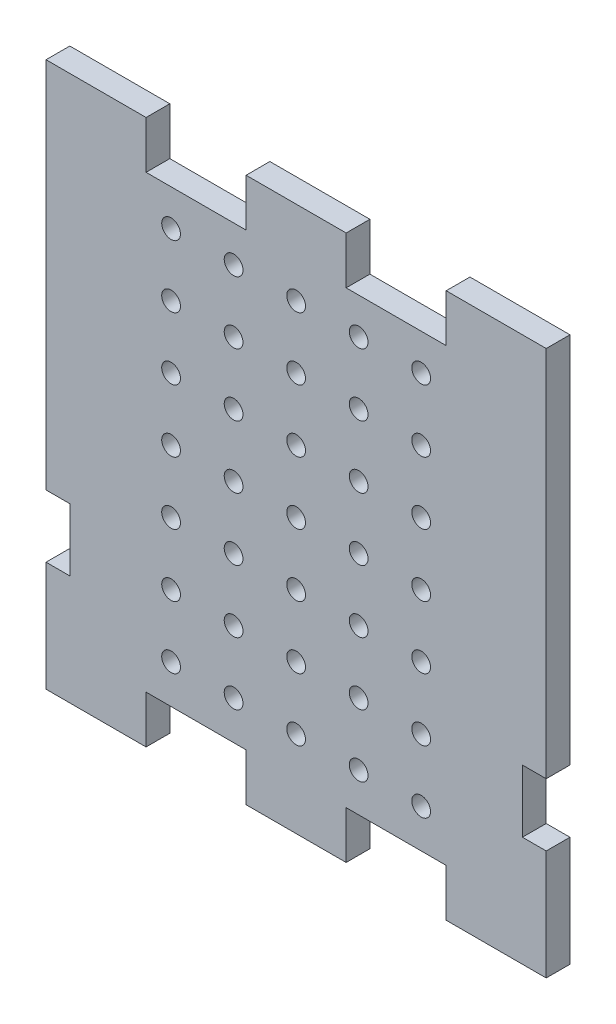
SolidWorks part; units mm, degrees
ref_plane "Front Plane" through (0, 0, 0) normal (0, 0, 1) x (1, 0, 0)
ref_plane "Top Plane" through (0, 0, 0) normal (0, 1, 0) x (1, 0, 0)
ref_plane "Right Plane" through (0, 0, 0) normal (1, 0, 0) x (0, 0, -1)
sketch "Sketch1" plane through (0, 0, 0) normal (0, 0, 1) x (1, 0, 0)
  line L0 (0, 9.652) -> (20.32, 9.652) construction
  line L1 (0, 0) -> (101.6, 0)
  line L2 (0, 0) -> (0, 110.744)
  line L3 (0, 110.744) -> (101.6, 110.744)
  line L4 (101.6, 0) -> (101.6, 110.744)
  line L5 (20.32, 0) -> (40.64, 0)
  line L6 (20.32, 0) -> (20.32, 9.652)
  line L7 (20.32, 9.652) -> (40.64, 9.652)
  line L8 (40.64, 0) -> (40.64, 9.652)
  line L9 (60.96, 0) -> (81.28, 0)
  line L10 (60.96, 0) -> (60.96, 9.652)
  line L11 (60.96, 9.652) -> (81.28, 9.652)
  line L12 (81.28, 0) -> (81.28, 9.652)
  line L13 (40.64, 9.652) -> (60.96, 9.652) construction
  line L14 (101.6, 9.652) -> (81.28, 9.652) construction
  line L15 (0, 55.372) -> (101.6, 55.372) construction
  line L16 (101.6, 101.092) -> (81.28, 101.092) construction
  line L17 (40.64, 101.092) -> (60.96, 101.092) construction
  line L18 (0, 101.092) -> (20.32, 101.092) construction
  line L19 (81.28, 110.744) -> (81.28, 101.092)
  line L20 (60.96, 101.092) -> (81.28, 101.092)
  line L21 (60.96, 110.744) -> (60.96, 101.092)
  line L22 (60.96, 110.744) -> (81.28, 110.744)
  line L23 (40.64, 110.744) -> (40.64, 101.092)
  line L24 (20.32, 101.092) -> (40.64, 101.092)
  line L25 (20.32, 110.744) -> (20.32, 101.092)
  line L26 (20.32, 110.744) -> (40.64, 110.744)
  line L27 (0, 110.744) -> (101.6, 110.744)
  line L28 (101.6, 9.652) -> (81.28, 9.652) construction
  dimension "D1" = 110.744
  dimension "D2" = 101.6
  dimension "D3" = 9.652
extrude "Boss-Extrude1" add sketch "Sketch1" along normal blind 4.826 contours L25 L3 L2 L1 L6 L7 L8 L10 L11 L12 L4 L19 L20 L21 L23 L24 region at (50.8, 55.372, 0)
sketch "Sketch2" plane through (0, 0, 4.826) normal (0, 0, 1) x (1, 0, 0)
  circle A0 centre (50.8, 68.326) radius 1.905
  circle A1 centre (63.5, 68.326) radius 1.905
  circle A2 centre (76.2, 68.326) radius 1.905
  circle A3 centre (63.5, 81.026) radius 1.905
  circle A4 centre (76.2, 81.026) radius 1.905
  circle A5 centre (63.5, 93.726) radius 1.905
  circle A6 centre (76.2, 93.726) radius 1.905
  circle A11 centre (38.1, 68.326) radius 1.905
  circle A12 centre (25.4, 68.326) radius 1.905
  circle A13 centre (38.1, 81.026) radius 1.905
  circle A14 centre (25.4, 81.026) radius 1.905
  circle A15 centre (50.8, 106.426) radius 1.905 [skipped]
  circle A16 centre (50.8, 93.726) radius 1.905 [skipped]
  circle A17 centre (50.8, 81.026) radius 1.905 [skipped]
  circle A18 centre (50.8, 119.126) radius 1.905 [skipped]
  circle A19 centre (38.1, 93.726) radius 1.905
  circle A20 centre (25.4, 93.726) radius 1.905
  circle A25 centre (50.8, 81.026) radius 1.905
  circle A26 centre (50.8, 93.726) radius 1.905
  circle A29 centre (63.5, 68.326) radius 1.905 [skipped]
  circle A30 centre (76.2, 68.326) radius 1.905 [skipped]
  circle A31 centre (63.5, 55.626) radius 1.905
  circle A32 centre (76.2, 55.626) radius 1.905
  circle A33 centre (63.5, 42.926) radius 1.905
  circle A34 centre (76.2, 42.926) radius 1.905
  circle A35 centre (63.5, 30.226) radius 1.905
  circle A36 centre (76.2, 30.226) radius 1.905
  circle A37 centre (63.5, 17.526) radius 1.905
  circle A38 centre (76.2, 17.526) radius 1.905
  circle A39 centre (38.1, 55.626) radius 1.905
  circle A40 centre (25.4, 55.626) radius 1.905
  circle A41 centre (38.1, 42.926) radius 1.905
  circle A42 centre (25.4, 42.926) radius 1.905
  circle A43 centre (25.4, 68.326) radius 1.905 [skipped]
  circle A44 centre (38.1, 68.326) radius 1.905 [skipped]
  circle A45 centre (50.8, 55.626) radius 1.905 [skipped]
  circle A46 centre (50.8, 42.926) radius 1.905 [skipped]
  circle A47 centre (50.8, 30.226) radius 1.905 [skipped]
  circle A48 centre (50.8, 17.526) radius 1.905 [skipped]
  circle A49 centre (38.1, 30.226) radius 1.905
  circle A50 centre (25.4, 30.226) radius 1.905
  circle A51 centre (38.1, 17.526) radius 1.905
  circle A52 centre (25.4, 17.526) radius 1.905
  circle A53 centre (50.8, 55.626) radius 1.905
  circle A54 centre (50.8, 42.926) radius 1.905
  circle A55 centre (50.8, 30.226) radius 1.905
  circle A56 centre (50.8, 17.526) radius 1.905
  circle A57 centre (63.5, 106.426) radius 1.905 [skipped]
  circle A58 centre (76.2, 106.426) radius 1.905 [skipped]
  circle A59 centre (63.5, 119.126) radius 1.905 [skipped]
  circle A60 centre (76.2, 119.126) radius 1.905 [skipped]
  circle A61 centre (38.1, 106.426) radius 1.905 [skipped]
  circle A62 centre (25.4, 106.426) radius 1.905 [skipped]
  circle A63 centre (38.1, 119.126) radius 1.905 [skipped]
  circle A64 centre (25.4, 119.126) radius 1.905 [skipped]
  circle A65 centre (50.8, 106.426) radius 1.905 [skipped]
  circle A66 centre (50.8, 119.126) radius 1.905 [skipped]
  dimension "D1" = 3.81
  dimension "D2" = 3
  dimension "D3" = 5
  dimension "D4" = 3
  dimension "D5" = 5
  dimension "D6" = 3
  dimension "D7" = 5
  dimension "D8" = 3
  dimension "D9" = 5
extrude "Cut-Extrude1" cut sketch "Sketch2" against normal through all
sketch "Sketch4" plane through (0, 0, 4.826) normal (0, 0, 1) x (1, 0, 0)
  line L0 (0, 35.052) -> (4.826, 35.052) construction
  line L1 (0, 35.052) -> (4.826, 35.052)
  line L2 (0, 22.352) -> (4.826, 22.352) construction
  line L3 (4.826, 35.052) -> (4.826, 22.352) construction
  line L4 (0, 35.052) -> (0, 22.352) construction
  line L5 (96.774, 35.052) -> (96.774, 22.352) construction
  line L6 (96.774, 22.352) -> (101.6, 22.352) construction
  line L7 (96.774, 35.052) -> (101.6, 35.052) construction
  line L8 (101.6, 35.052) -> (101.6, 22.352) construction
  line L9 (0, 22.352) -> (4.826, 22.352)
  line L10 (4.826, 35.052) -> (4.826, 22.352)
  line L11 (0, 35.052) -> (0, 22.352)
  line L12 (0, 35.052) -> (4.826, 35.052)
  line L13 (96.774, 35.052) -> (96.774, 22.352)
  line L14 (96.774, 22.352) -> (101.6, 22.352)
  line L15 (96.774, 35.052) -> (101.6, 35.052)
  line L16 (101.6, 35.052) -> (101.6, 22.352)
extrude "Cut-Extrude2" cut sketch "Sketch4" against normal through all contours L1 L11 L9 L10 | L16 L15 L13 L14 region at (2.413, 28.702, 4.826) region at (99.187, 28.702, 4.826)
equation "\"MDF\"= 0.19in"
equation "\"PVCID\" = 2.067in"
equation "\"PVCOD\" = 2.375in"
equation "\"GenDiameter\"= 60mm"
equation "\"GenCutDiameter\" = 1.8in"
equation "\"GenCutDistance\" = 1"
equation "\"TowerHeight\" = 6in"
equation "\"TowerFrontBase\" = 3in"
equation "\"FunnelHeight\" = 1in"
equation "\"FunnelAngle\" = 20"
equation "\"TowerSideBase\" = 3in"
equation "\"TowerPanelLength\" = 2in"
equation "\"TowerPanelLeeway\" = 0.5in"
equation "\"BaseLength\" = 9in"
equation "\"BaseWidth\" = 10in"
equation "\"WheelHoleLength\" = 3.25in"
equation "\"WheelHoleWidth\" = 26mm"
equation "\"WheelHoleFromBack\" = 1.5in"
equation "\"DropLength\" = 1in"
equation "\"DropWidth\" = 8.5in"
equation "\"BumperWidth\" = 2in"
equation "\"SmallHexDiameter\" = 0.185in"
equation "\"SmallHexHeight\" = 0.701in"
equation "\"ScrewSize\" = 0.106in"
equation "\"BigHexDiameter\" = 0.251in"
equation "\"BigHexHeight\" = 0.374in"
equation "\"PCBThickness\" = 0.066in"
equation "\"ConnectorHeight\" = 0.517in"
equation "\"BoardHeight\" = 0.583in"
equation "\"UnoStackHeight\" = 1.351in"
equation "\"UnoStackWidth\" = 3.053in"
equation "\"UnoStackLength\" = 3.152in"
equation "\"HBridgeWidth\" = 1.797in"
equation "\"HBridgeLength\" = 2.236in"
equation "\"DSWidth\" = 1.820in"
equation "\"DSLength\" = 1.833in"
equation "\"StepperWidth\" = 1.799in"
equation "\"StepperLength\" = 2.248in"
equation "\"ULNWidth\" = 1.304in"
equation "\"ULNLength\" = 1.545in"
equation "\"VSwitchHeight\" = 0.392in"
equation "\"VSwitchWidth\" = 0.637in"
equation "\"VSwitchLength\" = 1.097in"
equation "\"SkateWheelDiameter\" = 80mm"
equation "\"SkateWheelThickness\" = 24mm"
equation "\"BaseDistance\" = 3in"
equation "\"DummyVar\" = 2in"
equation "\"D1@Sketch1\"=\"MDF\"*4+3.6in"
equation "\"D1@Boss-Extrude1\"=\"MDF\""
equation "\"D3@Sketch1\"=\"MDF\"*2"
